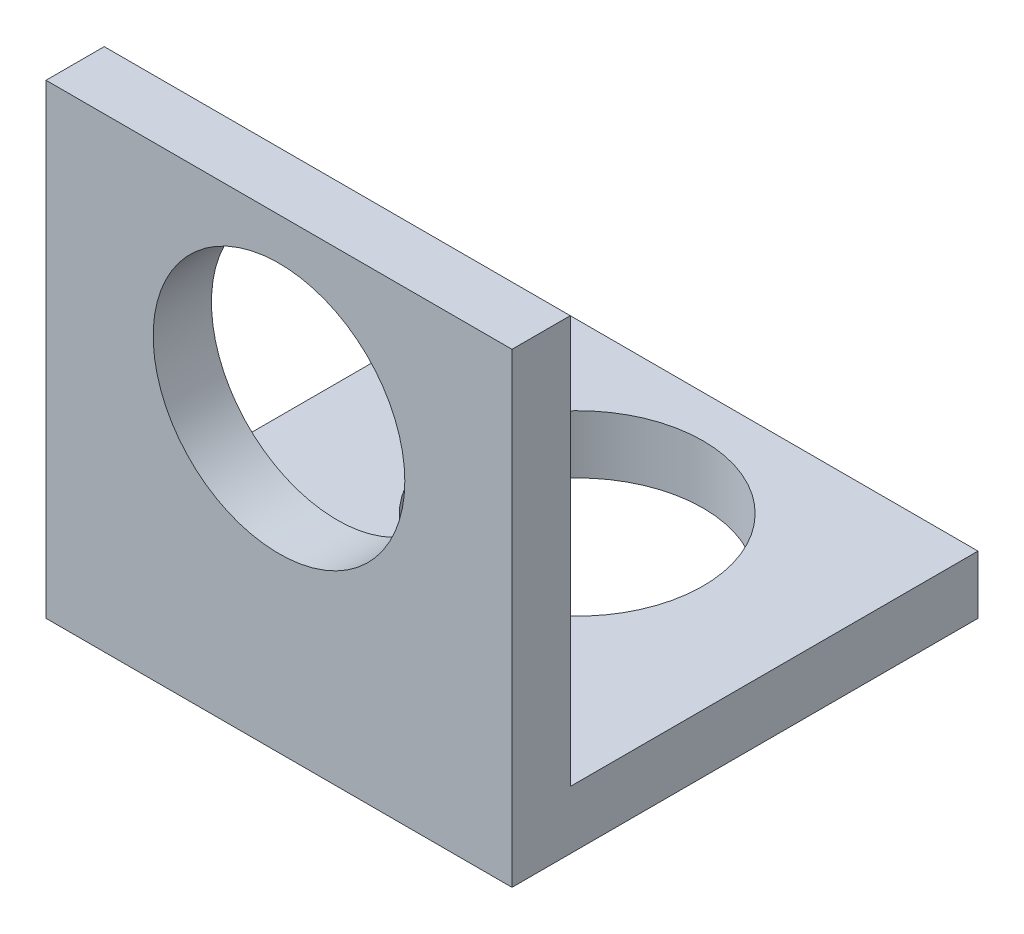
SolidWorks part; units mm, degrees
ref_plane "Front Plane" through (0, 0, 0) normal (0, 0, 1) x (1, 0, 0)
ref_plane "Top Plane" through (0, 0, 0) normal (0, 1, 0) x (1, 0, 0)
ref_plane "Right Plane" through (0, 0, 0) normal (1, 0, 0) x (0, 0, -1)
sketch "Sketch1" plane through (0, 0, 0) normal (1, 0, 0) x (0, 0, -1)
  line L0 (0, 0) -> (0, 12.7)
  line L1 (0, 0) -> (12.7, 0)
  line L2 (1.5875, 1.5875) -> (12.7, 1.5875)
  line L3 (1.5875, 1.5875) -> (1.5875, 12.7)
  line L4 (0, 12.7) -> (1.5875, 12.7)
  line L5 (12.7, 1.5875) -> (12.7, 0)
  dimension "D1" = 1.5875
  dimension "D2" = 12.7
extrude "Boss-Extrude1" add sketch "Sketch1" along normal blind 12.7
sketch "Sketch2" plane through (0, 0, 0) normal (0, 0, 1) x (1, 0, 0)
  line L0 (12.7, 12.7) -> (0, 12.7) construction
  line L1 (12.7, 12.7) -> (12.7, 0) construction
  circle A0 centre (6.35, 8.128) radius 3.429
  dimension "D1" = 4.572
  dimension "D3" = 6.858
  dimension "D2" = 6.35
extrude "Cut-Extrude1" cut sketch "Sketch2" against normal through all
sketch "Sketch3" plane through (0, 0, 0) normal (0, -1, 0) x (1, 0, 0)
  line L0 (12.7, -12.7) -> (0, -12.7) construction
  line L1 (0, 0) -> (0, -12.7) construction
  circle A0 centre (6.35, -8.128) radius 3.429
  point P6 (1.4139, -7.664)
  point P7 (5.912, -7.6135)
  dimension "D1" = 6.858
  dimension "D2" = 4.572
  dimension "D3" = 6.35
extrude "Cut-Extrude2" cut sketch "Sketch3" against normal through all
